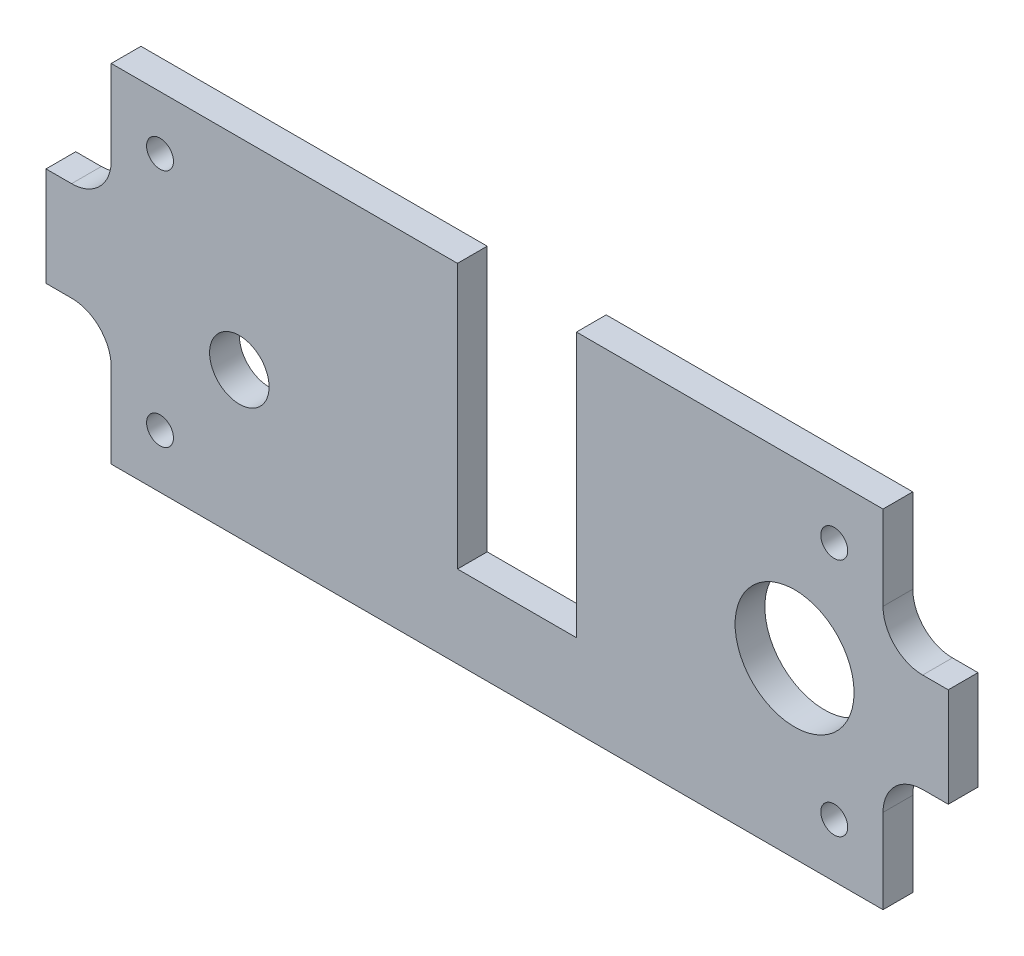
SolidWorks part; units mm, degrees
ref_plane "Front Plane" through (0, 0, 0) normal (0, 0, 1) x (1, 0, 0)
ref_plane "Top Plane" through (0, 0, 0) normal (0, 1, 0) x (1, 0, 0)
ref_plane "Right Plane" through (0, 0, 0) normal (1, 0, 0) x (0, 0, -1)
sketch "Sketch1" plane through (0, 0, 0) normal (0, 0, 1) x (1, 0, 0)
  line L16 (85.725, 56.3562) -> (85.725, 13.97)
  line L17 (85.725, 13.97) -> (66.675, 13.97)
  line L18 (66.675, 13.97) -> (66.675, 56.3562)
  line L19 (66.675, 56.3562) -> (11.2395, 56.3562)
  line L20 (11.2395, 56.3562) -> (11.2395, 42.8625)
  line L21 (4.8895, 36.5125) -> (0.7938, 36.5125)
  line L22 (0.7938, 36.5125) -> (0.7938, 20.6375)
  line L23 (0.7938, 20.6375) -> (4.8895, 20.6375)
  line L24 (11.2395, 14.2875) -> (11.2395, 0.7938)
  line L25 (11.2395, 0.7938) -> (134.8105, 0.7938)
  line L26 (134.8105, 0.7938) -> (134.8105, 14.2875)
  line L27 (141.1605, 20.6375) -> (145.2563, 20.6375)
  line L28 (145.2563, 20.6375) -> (145.2563, 36.5125)
  line L29 (145.2563, 36.5125) -> (141.1605, 36.5125)
  line L30 (134.8105, 42.8625) -> (134.8105, 56.3562)
  line L31 (134.8105, 56.3562) -> (85.725, 56.3562)
  line L32 (85.725, 56.3562) -> (85.725, 13.97)
  line L33 (85.725, 13.97) -> (66.675, 13.97)
  line L34 (66.675, 13.97) -> (66.675, 56.3562)
  line L35 (66.675, 56.3562) -> (11.2395, 56.3562)
  line L36 (11.2395, 56.3562) -> (11.2395, 42.8625)
  line L37 (4.8895, 36.5125) -> (0.7938, 36.5125)
  line L38 (0.7938, 36.5125) -> (0.7938, 20.6375)
  line L39 (0.7938, 20.6375) -> (4.8895, 20.6375)
  line L40 (11.2395, 14.2875) -> (11.2395, 0.7938)
  line L41 (11.2395, 0.7938) -> (134.8105, 0.7938)
  line L42 (134.8105, 0.7938) -> (134.8105, 14.2875)
  line L43 (141.1605, 20.6375) -> (145.2563, 20.6375)
  line L44 (145.2563, 20.6375) -> (145.2563, 36.5125)
  line L45 (145.2563, 36.5125) -> (141.1605, 36.5125)
  line L46 (134.8105, 42.8625) -> (134.8105, 56.3562)
  line L47 (134.8105, 56.3562) -> (85.725, 56.3562)
  arc A4 (4.8895, 36.5125) -> (11.2395, 42.8625) centre (4.8895, 42.8625) ccw
  arc A5 (11.2395, 14.2875) -> (4.8895, 20.6375) centre (4.8895, 14.2875) ccw
  arc A6 (141.1605, 20.6375) -> (134.8105, 14.2875) centre (141.1605, 14.2875) ccw
  arc A7 (134.8105, 42.8625) -> (141.1605, 36.5125) centre (141.1605, 42.8625) ccw
  arc A8 (4.8895, 36.5125) -> (11.2395, 42.8625) centre (4.8895, 42.8625) ccw
  arc A9 (11.2395, 14.2875) -> (4.8895, 20.6375) centre (4.8895, 14.2875) ccw
  arc A10 (141.1605, 20.6375) -> (134.8105, 14.2875) centre (141.1605, 14.2875) ccw
  arc A11 (134.8105, 42.8625) -> (141.1605, 36.5125) centre (141.1605, 42.8625) ccw
  dimension "D1" = 0
extrude "Boss-Extrude1" add sketch "Sketch1" along normal blind 4.7625
hole_wizard "3/8 (0.375) Diameter Hole1" positions "Sketch3" profile "Sketch2" hole size "3/8" standard "ANSI Inch" end condition through all
sketch "Sketch3" plane through (0, 0, 4.7625) normal (0, 0, 1) x (1, 0, 0)
  point P2 (31.75, 24.13)
sketch "Sketch2" plane through (31.75, 24.13, 4.7625) normal (1, 0, 0) x (0, -1, 0)
  line L0 (0, 0) -> (0, 4.7625)
  line L1 (0, 4.7625) -> (4.7625, 4.7625)
  line L2 (4.7625, 4.7625) -> (4.7625, 0)
  line L5 (4.7625, 0) -> (0, 0)
  line L11 (0, -6.35) -> (0, 107.95) construction
  dimension "Thru Hole Dia." = 9.525
  dimension "Thru Hole Depth" = 4.7625
hole_wizard "3/4 (0.75) Diameter Hole1" positions "Sketch5" profile "Sketch4" hole size "3/4" standard "ANSI Inch" end condition through all
sketch "Sketch5" plane through (0, 0, 4.7625) normal (0, 0, 1) x (1, 0, 0)
  point P0 (76.2, 28.575)
  point P3 (120.65, 28.575)
sketch "Sketch4" plane through (76.2, 28.575, 4.7625) normal (1, 0, 0) x (0, -1, 0)
  line L0 (0, 0) -> (0, 4.7625)
  line L1 (0, 4.7625) -> (9.525, 4.7625)
  line L2 (9.525, 4.7625) -> (9.525, 0)
  line L5 (9.525, 0) -> (0, 0)
  line L11 (0, -6.35) -> (0, 107.95) construction
  dimension "Thru Hole Dia." = 19.05
  dimension "Thru Hole Depth" = 4.7625
hole_wizard "#6 Clearance Hole1" positions "Sketch7" profile "Sketch6" hole size "#6" standard "ANSI Inch" end condition through all
sketch "Sketch7" plane through (0, 0, 4.7625) normal (0, 0, 1) x (1, 0, 0)
  point P0 (19.05, 9.398)
  point P3 (19.05, 47.752)
  point P6 (127, 47.752)
  point P9 (127, 9.398)
sketch "Sketch6" plane through (19.05, 9.398, 4.7625) normal (1, 0, 0) x (0, -1, 0)
  line L0 (0, 0) -> (0, 4.7625)
  line L1 (0, 4.7625) -> (2.1526, 4.7625)
  line L2 (2.1526, 4.7625) -> (2.1526, 0)
  line L5 (2.1526, 0) -> (0, 0)
  line L11 (0, -6.35) -> (0, 107.95) construction
  dimension "Thru Hole Dia." = 4.3053
  dimension "Thru Hole Depth" = 4.7625
